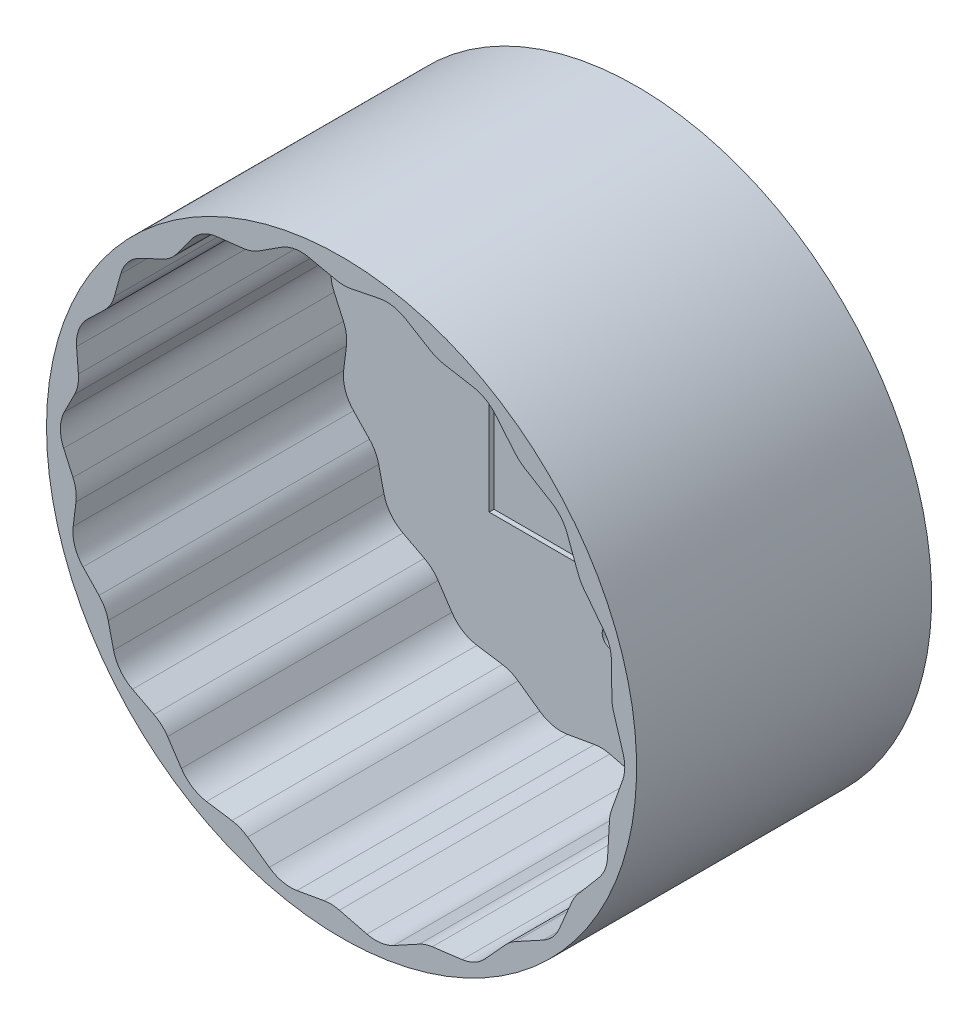
SolidWorks part; units mm, degrees
material "6061-T6 (SS)"
ref_plane "Front Plane" through (0, 0, 0) normal (0, 0, 1) x (1, 0, 0)
ref_plane "Top Plane" through (0, 0, 0) normal (0, 1, 0) x (1, 0, 0)
ref_plane "Right Plane" through (0, 0, 0) normal (1, 0, 0) x (0, 0, -1)
sketch "Sketch1" plane through (0, 0, 0) normal (0, 0, 1) x (1, 0, 0)
  circle A0 centre (0, 0) radius 76.2
  circle A1 centre (0.8288, 0) radius 69.85
  dimension "D1" = 152.4
  dimension "D2" = 139.7
extrude "Boss-Extrude1" add sketch "Sketch1" along normal blind 76.2
sketch "Sketch3" plane through (0, 0, 0) normal (0, 0, 1) x (1, 0, 0)
  circle A0 centre (0, 0) radius 76.2
extrude "Boss-Extrude2" add sketch "Sketch3" along normal blind 6.35
sketch "Sketch4" plane through (0, 0, 6.35) normal (0, 0, 1) x (1, 0, 0)
  line L1 (-31.75, 31.75) -> (31.75, 31.75)
  line L2 (-31.75, 31.75) -> (-31.75, -31.75)
  line L3 (-31.75, -31.75) -> (31.75, -31.75)
  line L4 (31.75, 31.75) -> (31.75, -31.75)
  point P5 (0, 31.75)
  point P7 (-31.75, 0)
  dimension "D1" = 63.5
  dimension "2.5" = 63.5
extrude "Cut-Extrude1" cut sketch "Sketch4" against normal blind 1.27
sketch "Sketch5" plane through (0, 0, 6.35) normal (0, 0, 1) x (1, 0, 0)
  line L0 (-31.75, 31.75) -> (-31.75, -31.75) construction
  line L1 (31.75, 31.75) -> (-31.75, 31.75) construction
  line L2 (31.75, -31.75) -> (31.75, 31.75) construction
  line L3 (-31.75, -31.75) -> (31.75, -31.75) construction
  circle A0 centre (0, 44.163) radius 2.54
  circle A1 centre (44.163, 0) radius 2.54
  circle A2 centre (-44.163, 0) radius 2.54
  circle A3 centre (0, -44.163) radius 2.54
  dimension "D1" = 5.08
  dimension "D2" = 5.08
  dimension "D3" = 5.08
  dimension "D4" = 5.08
  dimension "D5" = 12.413
  dimension "D6" = 12.413
  dimension "D7" = 12.413
  dimension "D8" = 12.413
extrude "Cut-Extrude2" cut sketch "Sketch5" against normal through all
sketch "Sketch10" plane through (0, 0, 76.2) normal (0, 0, 1) x (1, 0, 0)
  line L1 (69.266, -13.9779) -> (73.6417, -1.6437)
  line L2 (73.6417, -1.6437) -> (69.827, 10.8754)
  line L3 (69.827, 10.8754) -> (69.6537, 23.9617)
  line L4 (69.6537, 23.9617) -> (61.6625, 34.3261)
  line L5 (61.6625, 34.3261) -> (57.0633, 46.5787)
  line L6 (57.0633, 46.5787) -> (45.8812, 53.3789)
  line L7 (45.8812, 53.3789) -> (37.4785, 63.4126)
  line L8 (37.4785, 63.4126) -> (24.5898, 65.6844)
  line L9 (24.5898, 65.6844) -> (13.3778, 72.435)
  line L10 (13.3778, 72.435) -> (0.5484, 69.8494)
  line L11 (0.5484, 69.8494) -> (-12.2389, 72.6361)
  line L12 (-12.2389, 72.6361) -> (-23.2531, 65.5674)
  line L16 (-23.2531, 65.5674) -> (-36.2599, 64.1172)
  line L17 (-36.2599, 64.1172) -> (-44.0018, 53.5653)
  line L18 (-44.0018, 53.5653) -> (-55.8562, 48.0196)
  line L19 (-55.8562, 48.0196) -> (-59.3776, 35.4149)
  line L20 (-59.3776, 35.4149) -> (-68.7947, 26.3265)
  line L21 (-68.7947, 26.3265) -> (-67.7469, 13.2811)
  line L22 (-67.7469, 13.2811) -> (-73.6427, 1.597)
  line L23 (-73.6427, 1.597) -> (-68.2532, -10.3292)
  line L24 (-68.2532, -10.3292) -> (-69.8724, -23.316)
  line L25 (-69.8724, -23.316) -> (-68.2532, -10.3292)
  line L26 (-68.2532, -10.3292) -> (-69.8724, -23.316)
  line L27 (-69.8724, -23.316) -> (-60.8454, -32.7919)
  line L28 (-60.8454, -32.7919) -> (-57.8939, -45.5422)
  line L29 (-57.8939, -45.5422) -> (-46.2793, -51.5737)
  line L30 (-46.2793, -51.5737) -> (-39.0297, -62.4698)
  line L31 (-39.0297, -62.4698) -> (-26.0935, -64.4532)
  line L32 (-26.0935, -64.4532) -> (-15.4208, -72.0277)
  line L33 (-15.4208, -72.0277) -> (-2.5298, -69.7692)
  line L34 (-2.5298, -69.7692) -> (10.1639, -72.9554)
  line L35 (10.1639, -72.9554) -> (21.6463, -66.6758)
  line L36 (21.6463, -66.6758) -> (34.6277, -65.0132)
  line L37 (34.6277, -65.0132) -> (43.4458, -55.3427)
  line L38 (43.4458, -55.3427) -> (54.9334, -49.0725)
  line L39 (54.9334, -49.0725) -> (60.056, -37.0293)
  line L40 (60.056, -37.0293) -> (68.5159, -27.0438)
  line L41 (68.5159, -27.0438) -> (69.266, -13.9779)
  circle A7 centre (0, 0) radius 73.66 construction
  circle A8 centre (0.8288, 0) radius 69.85 construction
  circle A9 centre (0.8288, 0) radius 69.85 construction
  circle M41 centre (0.8288, 0) radius 69.85
  dimension "D1" = 147.32
extrude "Cut-Extrude10" cut sketch "Sketch10" against normal up to surface (69.85 mm away) contours M41 | L20 L21 M41 | L18 L19 M41 | L16 L17 M41 | L11 L12 M41 | L9 L10 M41 | L7 L8 M41 | L5 L6 M41 | L3 L4 M41 | L1 L2 M41 | L40 L41 M41 | L38 L39 M41 | L36 L37 M41 | L34 L35 M41 | L32 L33 M41 | L30 L31 M41 | L28 L29 M41 | L24 L27 M41 | L22 L23 M41 | L19 L20 L21 L22 L23 L24 L25 L26 L27 L28 L29 L30 L31 L32 L33 L34 L35 L36 L37 L38 L39 L40 L41 L1 L2 L3 L4 L5 L6 L7 L8 L9 L10 L11 L12 L16 L17 L18 region at (71.4363, -1.5939, 76.2) region at (66.4312, -26.2109, 76.2) region at (0.8288, 0, 76.2) region at (53.1944, -47.4952, 76.2) region at (67.5417, 23.2264, 76.2) region at (33.4742, -62.7945, 76.2) region at (55.2676, 45.0914, 76.2) region at (9.8233, -70.2935, 76.2) region at (36.2379, 61.2661, 76.2) region at (-14.7884, -69.2247, 76.2) region at (12.9238, 69.8144, 76.2) region at (-37.3904, -59.9006, 76.2) region at (-11.7343, 69.8312, 76.2) region at (-55.3763, -43.5897, 76.2) region at (-34.7441, 61.4968, 76.2) region at (-66.7635, -22.2908, 76.2) region at (-53.4365, 45.9699, 76.2) region at (-70.3423, 1.5262, 76.2) region at (-65.74, 25.1715, 76.2) up to face at (2.54, 44.163, 6.35)
fillet "Fillet1" radius 9.525 36 edges at (-73.6427, 1.597, 41.275) (-69.8724, -23.316, 41.275) (-68.2532, -10.3292, 41.275) (-60.8454, -32.7919, 41.275) (-57.8939, -45.5422, 41.275) (-46.2793, -51.5737, 41.275) (-39.0297, -62.4698, 41.275) (-26.0935, -64.4532, 41.275) (-15.4208, -72.0277, 41.275) (-2.5298, -69.7692, 41.275) (10.1639, -72.9554, 41.275) (21.6463, -66.6758, 41.275) (34.6277, -65.0132, 41.275) (43.4458, -55.3427, 41.275) (54.9334, -49.0725, 41.275) (60.056, -37.0293, 41.275) (68.5159, -27.0438, 41.275) (69.266, -13.9779, 41.275) (73.6417, -1.6437, 41.275) (69.827, 10.8754, 41.275) (69.6537, 23.9617, 41.275) (61.6625, 34.3261, 41.275) (57.0633, 46.5787, 41.275) (45.8812, 53.3789, 41.275) (37.4785, 63.4126, 41.275) (24.5898, 65.6844, 41.275) (13.3778, 72.435, 41.275) (0.5484, 69.8494, 41.275) (-12.2389, 72.6361, 41.275) (-23.2531, 65.5674, 41.275) (-36.2599, 64.1172, 41.275) (-44.0018, 53.5653, 41.275) (-55.8562, 48.0196, 41.275) (-59.3776, 35.4149, 41.275) (-68.7947, 26.3265, 41.275) (-67.7469, 13.2811, 41.275)
